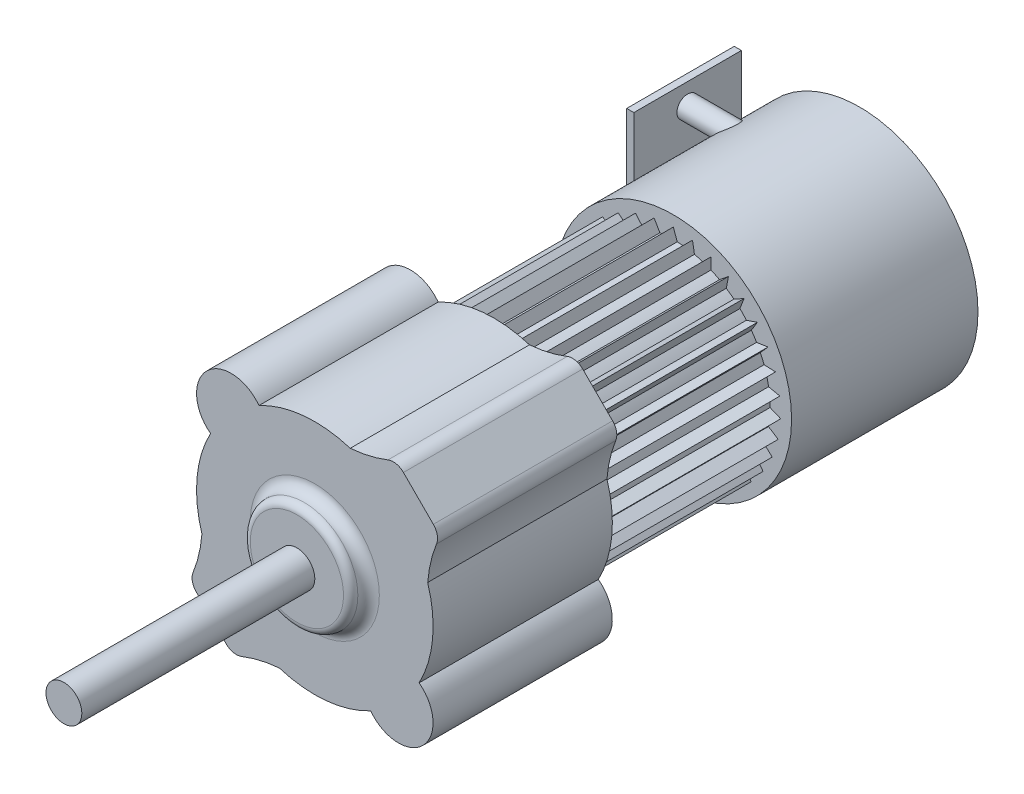
SolidWorks part; units mm, degrees
ref_plane "Front Plane" through (0, 0, 0) normal (0, 0, 1) x (1, 0, 0)
ref_plane "Top Plane" through (0, 0, 0) normal (0, 1, 0) x (1, 0, 0)
ref_plane "Right Plane" through (0, 0, 0) normal (1, 0, 0) x (0, 0, -1)
sketch "Sketch1" plane through (0, 0, 0) normal (0, 0, 1) x (1, 0, 0)
  line L0 (11.392, 17.5) -> (17.5, 11.392)
  line L7 (-17.5, -11.392) -> (-11.392, -17.5)
  arc A0 (-14.5435, 7.7934) -> (-15.7433, -4.9394) centre (0, 0) ccw
  arc A1 (-7.7934, 14.5435) -> (-14.5435, 7.7934) centre (-11.6673, 11.6673) ccw
  arc A2 (14.5435, -7.7934) -> (7.7934, -14.5435) centre (11.6673, -11.6673) cw
  arc A3 (4.9394, 15.7433) -> (-7.7934, 14.5435) centre (0, 0) ccw
  arc A4 (14.5435, -7.7934) -> (15.7433, 4.9394) centre (0, 0) ccw
  arc A5 (-4.9394, -15.7433) -> (7.7934, -14.5435) centre (0, 0) ccw
  spline S0 degree 2 poles (11.392, 17.5) (8.3367, 16.021) (4.9394, 15.7433) knots 0 0 0 1 1 1
  spline S1 degree 2 poles (-17.5, -11.392) (-16.021, -8.3367) (-15.7433, -4.9394) knots 0 0 0 1 1 1
  spline S2 degree 2 poles (-11.392, -17.5) (-8.3367, -16.021) (-4.9394, -15.7433) knots 0 0 0 1 1 1
  spline S3 degree 2 poles (17.5, 11.392) (16.021, 8.3367) (15.7433, 4.9394) knots 0 0 0 1 1 1
  point P0 (0, 0)
extrude "Boss-Extrude1" add sketch "Sketch1" along normal blind 25
fillet "Fillet1" radius 2 4 edges at (-11.392, -17.5, 12.5) (-17.5, -11.392, 12.5) (17.5, 11.392, 12.5) (11.392, 17.5, 12.5)
sketch "Sketch3" plane through (0, 0, 0) normal (0, 0, -1) x (-1, 0, 0)
  line L3 (-0.552, 13.4887) -> (0, 15)
  line L4 (0, 15) -> (0.552, 13.4887)
  line L5 (2.6784, 14.7589) -> (2.9516, 13.1734)
  line L6 (1.8654, 13.3705) -> (2.6784, 14.7589)
  line L7 (5.2706, 14.0435) -> (5.2564, 12.4347)
  line L8 (4.2228, 12.8225) -> (5.2706, 14.0435)
  line L9 (7.6935, 12.8767) -> (7.3922, 11.2963)
  line L10 (6.4445, 11.8625) -> (7.6935, 12.8767)
  line L11 (9.8691, 11.2961) -> (9.2904, 9.7948)
  line L12 (8.4591, 10.5211) -> (9.8691, 11.2961)
  line L13 (11.7275, 9.3523) -> (10.89, 7.9785)
  line L14 (10.2018, 8.8416) -> (11.7275, 9.3523)
  line L15 (13.2089, 7.108) -> (12.1397, 5.9058)
  line L16 (11.6165, 6.8779) -> (13.2089, 7.108)
  line L17 (14.2658, 4.6353) -> (12.9991, 3.6433)
  line L18 (12.658, 4.6932) -> (14.2658, 4.6353)
  line L19 (14.8642, 2.0135) -> (13.4407, 1.2637)
  line L20 (13.2925, 2.3576) -> (14.8642, 2.0135)
  line L21 (14.9849, -0.673) -> (13.4504, -1.1566)
  line L22 (13.4999, -0.0538) -> (14.9849, -0.673)
  line L23 (14.6239, -3.3378) -> (13.0277, -3.5396)
  line L24 (13.2733, -2.4634) -> (14.6239, -3.3378)
  line L25 (13.7929, -5.8954) -> (12.1863, -5.809)
  line L26 (12.6202, -4.7939) -> (13.7929, -5.8954)
  line L27 (12.5186, -8.2635) -> (10.9532, -7.8915)
  line L28 (11.5614, -6.9702) -> (12.5186, -8.2635)
  line L29 (10.8419, -10.3659) -> (9.3681, -9.7205)
  line L30 (10.131, -8.9226) -> (10.8419, -10.3659)
  line L31 (8.8168, -12.1353) -> (7.4819, -11.237)
  line L32 (8.375, -10.5882) -> (8.8168, -12.1353)
  line L33 (6.5083, -13.5145) -> (5.3552, -12.3924)
  line L34 (6.3498, -11.9134) -> (6.5083, -13.5145)
  line L35 (3.9906, -14.4594) -> (3.0564, -13.1495)
  line L36 (4.1206, -12.8558) -> (3.9906, -14.4594)
  line L37 (1.3446, -14.9396) -> (0.6594, -13.4839)
  line L38 (1.7589, -13.3849) -> (1.3446, -14.9396)
  line L39 (-1.3446, -14.9396) -> (-1.7589, -13.3849)
  line L40 (-0.6594, -13.4839) -> (-1.3446, -14.9396)
  line L41 (-3.9906, -14.4594) -> (-4.1206, -12.8558)
  line L42 (-3.0564, -13.1495) -> (-3.9906, -14.4594)
  line L43 (-6.5083, -13.5145) -> (-6.3498, -11.9134)
  line L44 (-5.3552, -12.3924) -> (-6.5083, -13.5145)
  line L45 (-8.8168, -12.1353) -> (-8.375, -10.5882)
  line L46 (-7.4819, -11.237) -> (-8.8168, -12.1353)
  line L47 (-10.8419, -10.3659) -> (-10.131, -8.9226)
  line L48 (-9.3681, -9.7205) -> (-10.8419, -10.3659)
  line L49 (-12.5186, -8.2635) -> (-11.5614, -6.9702)
  line L50 (-10.9532, -7.8915) -> (-12.5186, -8.2635)
  line L51 (-13.7929, -5.8954) -> (-12.6202, -4.7939)
  line L52 (-12.1863, -5.809) -> (-13.7929, -5.8954)
  line L53 (-14.6239, -3.3378) -> (-13.2733, -2.4634)
  line L54 (-13.0277, -3.5396) -> (-14.6239, -3.3378)
  line L55 (-14.9849, -0.673) -> (-13.4999, -0.0538)
  line L56 (-13.4504, -1.1566) -> (-14.9849, -0.673)
  line L57 (-14.8642, 2.0135) -> (-13.2925, 2.3576)
  line L58 (-13.4407, 1.2637) -> (-14.8642, 2.0135)
  line L59 (-14.2658, 4.6353) -> (-12.658, 4.6932)
  line L60 (-12.9991, 3.6433) -> (-14.2658, 4.6353)
  line L61 (-13.2089, 7.108) -> (-11.6165, 6.8779)
  line L62 (-12.1397, 5.9058) -> (-13.2089, 7.108)
  line L63 (-11.7275, 9.3523) -> (-10.2018, 8.8416)
  line L64 (-10.89, 7.9785) -> (-11.7275, 9.3523)
  line L65 (-9.8691, 11.2961) -> (-8.4591, 10.5211)
  line L66 (-9.2904, 9.7948) -> (-9.8691, 11.2961)
  line L67 (-7.6935, 12.8767) -> (-6.4445, 11.8625)
  line L68 (-7.3922, 11.2963) -> (-7.6935, 12.8767)
  line L69 (-5.2706, 14.0435) -> (-4.2228, 12.8225)
  line L70 (-5.2564, 12.4347) -> (-5.2706, 14.0435)
  line L71 (-2.6784, 14.7589) -> (-1.8654, 13.3705)
  line L72 (-2.9516, 13.1734) -> (-2.6784, 14.7589)
  arc A1 (1.8654, 13.3705) -> (0.552, 13.4887) centre (0, 0) ccw
  arc A2 (4.2228, 12.8225) -> (2.9516, 13.1734) centre (0, 0) ccw
  arc A3 (6.4445, 11.8625) -> (5.2564, 12.4347) centre (0, 0) ccw
  arc A4 (8.4591, 10.5211) -> (7.3922, 11.2963) centre (0, 0) ccw
  arc A5 (10.2018, 8.8416) -> (9.2904, 9.7948) centre (0, 0) ccw
  arc A6 (11.6165, 6.8779) -> (10.89, 7.9785) centre (0, 0) ccw
  arc A7 (12.658, 4.6932) -> (12.1397, 5.9058) centre (0, 0) ccw
  arc A8 (13.2925, 2.3576) -> (12.9991, 3.6433) centre (0, 0) ccw
  arc A9 (13.4999, -0.0538) -> (13.4407, 1.2637) centre (0, 0) ccw
  arc A10 (13.2733, -2.4634) -> (13.4504, -1.1566) centre (0, 0) ccw
  arc A11 (12.6202, -4.7939) -> (13.0277, -3.5396) centre (0, 0) ccw
  arc A12 (11.5614, -6.9702) -> (12.1863, -5.809) centre (0, 0) ccw
  arc A13 (10.131, -8.9226) -> (10.9532, -7.8915) centre (0, 0) ccw
  arc A14 (8.375, -10.5882) -> (9.3681, -9.7205) centre (0, 0) ccw
  arc A15 (6.3498, -11.9134) -> (7.4819, -11.237) centre (0, 0) ccw
  arc A16 (4.1206, -12.8558) -> (5.3552, -12.3924) centre (0, 0) ccw
  arc A17 (1.7589, -13.3849) -> (3.0564, -13.1495) centre (0, 0) ccw
  arc A18 (-0.6594, -13.4839) -> (0.6594, -13.4839) centre (0, 0) ccw
  arc A19 (-3.0564, -13.1495) -> (-1.7589, -13.3849) centre (0, 0) ccw
  arc A20 (-5.3552, -12.3924) -> (-4.1206, -12.8558) centre (0, 0) ccw
  arc A21 (-0.552, 13.4887) -> (-1.8654, 13.3705) centre (0, 0) ccw
  arc A22 (-2.9516, 13.1734) -> (-4.2228, 12.8225) centre (0, 0) ccw
  arc A23 (-5.2564, 12.4347) -> (-6.4445, 11.8625) centre (0, 0) ccw
  arc A24 (-7.3922, 11.2963) -> (-8.4591, 10.5211) centre (0, 0) ccw
  arc A25 (-9.2904, 9.7948) -> (-10.2018, 8.8416) centre (0, 0) ccw
  arc A26 (-10.89, 7.9785) -> (-11.6165, 6.8779) centre (0, 0) ccw
  arc A27 (-12.1397, 5.9058) -> (-12.658, 4.6932) centre (0, 0) ccw
  arc A28 (-12.9991, 3.6433) -> (-13.2925, 2.3576) centre (0, 0) ccw
  arc A29 (-13.4407, 1.2637) -> (-13.4999, -0.0538) centre (0, 0) ccw
  arc A30 (-13.4504, -1.1566) -> (-13.2733, -2.4634) centre (0, 0) ccw
  arc A31 (-13.0277, -3.5396) -> (-12.6202, -4.7939) centre (0, 0) ccw
  arc A32 (-12.1863, -5.809) -> (-11.5614, -6.9702) centre (0, 0) ccw
  arc A33 (-10.9532, -7.8915) -> (-10.131, -8.9226) centre (0, 0) ccw
  arc A34 (-9.3681, -9.7205) -> (-8.375, -10.5882) centre (0, 0) ccw
  arc A35 (-7.4819, -11.237) -> (-6.3498, -11.9134) centre (0, 0) ccw
  point P111 (0, 0)
  dimension "D1" = 35
extrude "Boss-Extrude2" add sketch "Sketch3" along normal blind 25
sketch "Sketch4" plane through (0, 0, -25) normal (0, 0, -1) x (-1, 0, 0)
  circle A0 centre (0, 0) radius 16.5
extrude "Boss-Extrude5" add sketch "Sketch4" along normal blind 26 contours A0
sketch "Sketch6" plane through (0, 0, -51) normal (0, 0, -1) x (-1, 0, 0)
  line L1 (16.5, -15.079) -> (16.5, 15.079)
  line L2 (16.5, 15.079) -> (17.5, 15.079)
  line L3 (17.5, 15.079) -> (17.5, -15.079)
  line L4 (16.5, -15.079) -> (17.5, -15.079)
  point P11 (17.5, 0)
extrude "Boss-Extrude6" add sketch "Sketch6" against normal blind 15 separate body
sketch "Sketch7" plane through (-17.5, 0, 0) normal (-1, 0, 0) x (0, 0, 1)
  circle A0 centre (-43.5, 12.0662) radius 1.5
  circle A1 centre (-43.5, -12.0662) radius 1.5
extrude "Boss-Extrude9" add sketch "Sketch7" against normal blind 15
sketch "Sketch8" plane through (0, 0, 25) normal (0, 0, 1) x (1, 0, 0)
  circle A0 centre (0, 0) radius 2.5
extrude "Boss-Extrude10" add sketch "Sketch8" along normal blind 35
sketch "Sketch9" plane through (0, 0, 25) normal (0, 0, 1) x (1, 0, 0)
  circle A0 centre (0, 0) radius 7.5
extrude "Boss-Extrude11" add sketch "Sketch9" along normal blind 2.5
fillet "Fillet2" radius 1.5 1 edges at (7.5, 0, 25)
fillet "Fillet3" radius 1 1 edges at (7.5, 0, 27.5)
ref_point "Point1"
